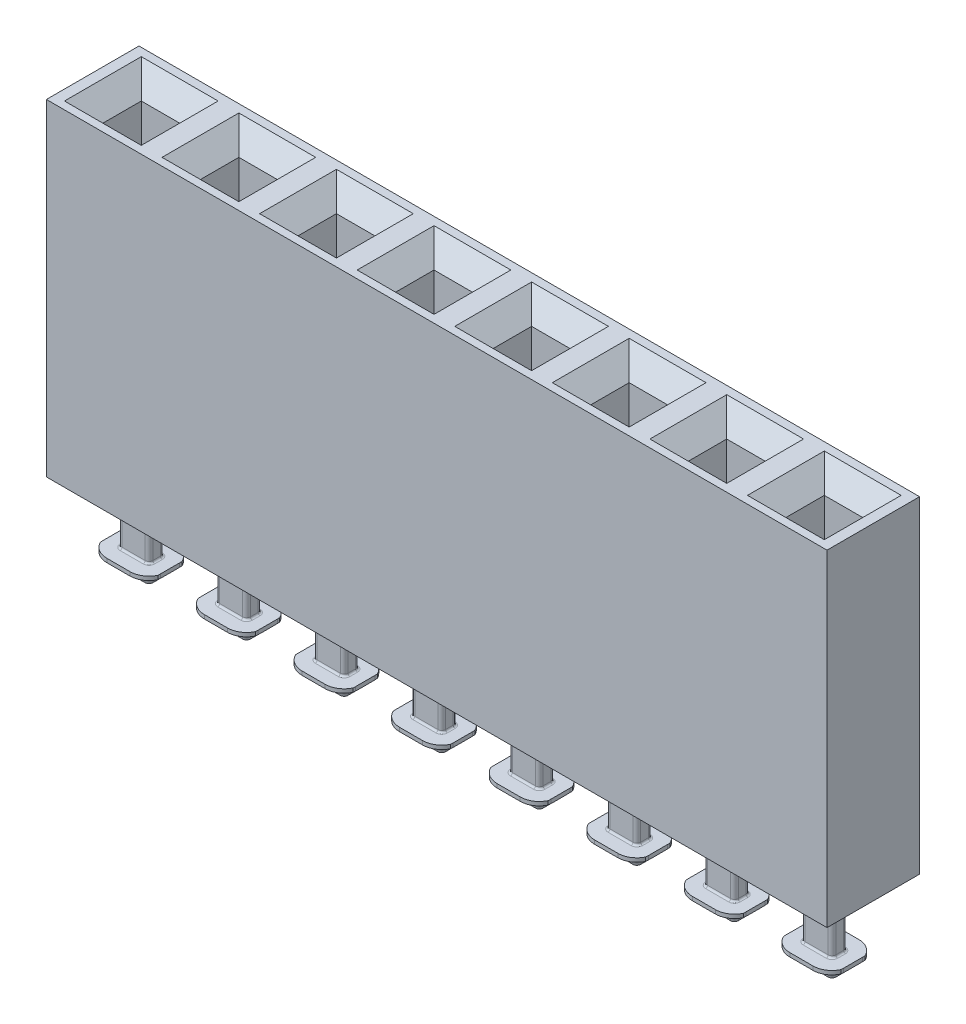
SolidWorks part; units mm, degrees
other "pin"
other "corpo" parameters "D1"=2.41, "D2"=2.41, "D3"=6.4991, "D4"=4.5449
ref_plane "Front Plane" through (0, 0, 0) normal (0, 0, 1) x (1, 0, 0)
ref_plane "Top Plane" through (0, 0, 0) normal (0, 1, 0) x (1, 0, 0)
ref_plane "Right Plane" through (0, 0, 0) normal (1, 0, 0) x (0, 0, -1)
sketch "Sketch1" plane through (0, 0, 0) normal (0, 1, 0) x (1, 0, 0)
  line L1 (-1.27, -1.2) -> (19.05, -1.2)
  line L2 (-1.27, -1.2) -> (-1.27, 1.21)
  line L3 (-1.27, 1.21) -> (19.05, 1.21)
  line L4 (19.05, -1.2) -> (19.05, 1.21)
  dimension "D1" = 2.41
  dimension "D2" = 20.32
  dimension "D3" = 1.21
  dimension "D4" = 1.27
extrude "Boss-Extrude1" add sketch "Sketch1" along normal blind 8.51
sketch "Sketch2" plane through (0, 8.51, 0) normal (0, 1, 0) x (1, 0, 0)
  line L1 (-0.5, 0.5) -> (0.5, 0.5)
  line L2 (-0.5, 0.5) -> (-0.5, -0.5)
  line L3 (-0.5, -0.5) -> (0.5, -0.5)
  line L4 (0.5, 0.5) -> (0.5, -0.5)
  line L5 (-0.5, 0.5) -> (0.5, -0.5) construction
  line L6 (-0.5, -0.5) -> (0.5, 0.5) construction
  point P0 (0, 0)
  dimension "D1" = 1
extrude "Cut-Extrude1" cut sketch "Sketch2" against normal blind 5
chamfer "Chamfer1" distance 0.5 angle 45 4 edges at (0.5, 8.51, 0) (0, 8.51, 0.5) (-0.5, 8.51, 0) (0, 8.51, -0.5)
pattern_linear "LPattern1" count 8 spacing 2.54 along (1, 0, 0) of "Cut-Extrude1", "Chamfer1"
sketch "Sketch3" plane through (0, 0, 0) normal (0, -1, 0) x (1, 0, 0)
  line L1 (-0.4, 0.2) -> (0.4, 0.2)
  line L2 (-0.4, 0.2) -> (-0.4, -0.2)
  line L3 (-0.4, -0.2) -> (0.4, -0.2)
  line L4 (0.4, 0.2) -> (0.4, -0.2)
  line L5 (-0.4, 0.2) -> (0.4, -0.2) construction
  line L6 (-0.4, -0.2) -> (0.4, 0.2) construction
  circle A0 centre (0, 0) radius 0.5 construction
  point P0 (0, 0)
  dimension "D3" = 1
  dimension "D1" = 0.4
  dimension "D2" = 0.8
extrude "Boss-Extrude2" add sketch "Sketch3" along normal blind 2.1 and the other way blind 3.51 separate body
sketch "Sketch6" plane through (0, 3.51, 0) normal (0, 1, 0) x (1, 0, 0)
  line L0 (-0.4, -0.2) -> (0.4, 0.2) construction
  circle A0 centre (0, 0) radius 0.4472
extrude "Cut-Extrude2" cut sketch "Sketch6" against normal through all
pattern_linear "LPattern4" count 8 spacing 2.54 along (1, 0, 0) of "Cut-Extrude2"
sketch "Sketch7" plane through (0, 3.51, 0) normal (0, 1, 0) x (1, 0, 0)
  line L4 (0.5, -0.5) -> (0.5, 0.5)
  line L5 (0.5, 0.5) -> (-0.5, 0.5)
  line L6 (-0.5, 0.5) -> (-0.5, -0.5)
  line L7 (-0.5, -0.5) -> (0.5, -0.5)
  line L8 (0.5, -0.5) -> (0.5, 0.5)
  line L9 (0.5, 0.5) -> (-0.5, 0.5)
  line L10 (-0.5, 0.5) -> (-0.5, -0.5)
  line L11 (-0.5, -0.5) -> (0.5, -0.5)
  dimension "D1" = 0
extrude "Boss-Extrude4" add sketch "Sketch7" along normal blind 0.5
fillet "Fillet3" radius 0.2 4 edges at (0.5, 3.76, -0.5) (-0.5, 3.76, -0.5) (-0.5, 3.76, 0.5) (0.5, 3.76, 0.5)
fillet "Fillet1" radius 0.1 4 edges at (0.4, 0.705, -0.2) (-0.4, 0.705, -0.2) (0.4, 0.705, 0.2) (-0.4, 0.705, 0.2)
sketch "Sketch4" plane through (0, -2.1, 0) normal (0, -1, 0) x (1, 0, 0)
  line L0 (0, -0.25) -> (0, 0.25) construction
  line L1 (-0.75, -0.25) -> (-0.75, 0.25)
  line L2 (0.75, -0.25) -> (0.75, 0.25)
  arc A0 (-0.75, -0.25) -> (0.75, -0.25) centre (0, -0.25) ccw
  arc A1 (0.75, 0.25) -> (-0.75, 0.25) centre (0, 0.25) ccw
  point P2 (0, 0)
  dimension "D1" = 0.5
  dimension "D2" = 1.5
extrude "Boss-Extrude3" add sketch "Sketch4" against normal blind 0.1 from offset 0.35 offset against normal yes
fillet "Fillet2" radius 0.4 6 edges at (0.3707, -1.75, 0.1707) (0.3707, -1.75, -0.1707) (0, -1.75, -0.2) (-0.3707, -1.75, -0.1707) (-0.3707, -1.75, 0.1707) (0, -1.75, 0.2)
fillet "Fillet4" radius 0.05 32 edges at (0.3707, 3.51, 0.1707) (0.4, 3.51, 0) (0.3707, 3.51, -0.1707) (0, 3.51, -0.2) (-0.3707, 3.51, -0.1707) (-0.4, 3.51, 0) (-0.3707, 3.51, 0.1707) (0, 3.51, 0.2) (-0.3707, -1.65, 0.1707) (-0.4, -1.65, 0) (-0.3707, -1.65, -0.1707) (0, -1.65, -0.2) (0.3707, -1.65, -0.1707) (0.4, -1.65, 0) (0.3707, -1.65, 0.1707) (-0.4414, 4.01, 0.4414) (-0.5, 4.01, 0) (-0.4414, 4.01, -0.4414) (0, 4.01, -0.5) (0.4414, 4.01, -0.4414) (0.5, 4.01, 0) (0.4414, 4.01, 0.4414) (-0.4414, 3.51, 0.4414) (-0.5, 3.51, 0) (-0.4414, 3.51, -0.4414) (0, 3.51, -0.5) (0.4414, 3.51, -0.4414) (0.5, 3.51, 0) (0.4414, 3.51, 0.4414) (0, -1.65, 0.2) (0, 4.01, 0.5) (0, 3.51, 0.5)
sketch "Sketch8" plane through (0, -2.1, 0) normal (0, -1, 0) x (1, 0, 0)
  line L3 (0.3, -0.5969) -> (-0.3, -0.5969)
  line L4 (0.3, -0.5969) -> (-0.3, -0.5969)
  line L5 (-0.3, 0.5969) -> (0.3, 0.5969)
  line L6 (-0.3, 0.5969) -> (0.3, 0.5969)
  arc A7 (-0.747, -0.3169) -> (-0.3, -0.5969) centre (-0.3, -0.1) ccw
  arc A8 (-0.747, -0.3169) -> (0.747, -0.3169) centre (0, -0.25) ccw
  arc A9 (0.3, -0.5969) -> (0.747, -0.3169) centre (0.3, -0.1) ccw
  arc A10 (-0.747, -0.3169) -> (-0.3, -0.5969) centre (-0.3, -0.1) ccw
  arc A11 (-0.747, -0.3169) -> (0.747, -0.3169) centre (0, -0.25) ccw
  arc A12 (0.3, -0.5969) -> (0.747, -0.3169) centre (0.3, -0.1) ccw
  arc A13 (0.747, 0.3169) -> (-0.747, 0.3169) centre (0, 0.25) ccw
  arc A14 (-0.3, 0.5969) -> (-0.747, 0.3169) centre (-0.3, 0.1) ccw
  arc A15 (0.747, 0.3169) -> (0.3, 0.5969) centre (0.3, 0.1) ccw
  arc A16 (0.747, 0.3169) -> (-0.747, 0.3169) centre (0, 0.25) ccw
  arc A17 (-0.3, 0.5969) -> (-0.747, 0.3169) centre (-0.3, 0.1) ccw
  arc A18 (0.747, 0.3169) -> (0.3, 0.5969) centre (0.3, 0.1) ccw
  dimension "D1" = 0
  dimension "D2" = 0
extrude "Cut-Extrude3" cut sketch "Sketch8" against normal up to surface (0.45 mm away) up to face at (0, -1.65, 0)
pattern_linear "LPattern5" count 8 spacing 2.54 along (1, 0, 0) of bodies 122 105
equation "\"pin\"= 8"
equation "\"D2@Sketch1\"=\"pin\"*2.54"
equation "\"D1@LPattern1\"=\"pin\""
equation "\"D1@LPattern4\"=\"pin\""
equation "\"D1@LPattern5\"=\"pin\""
